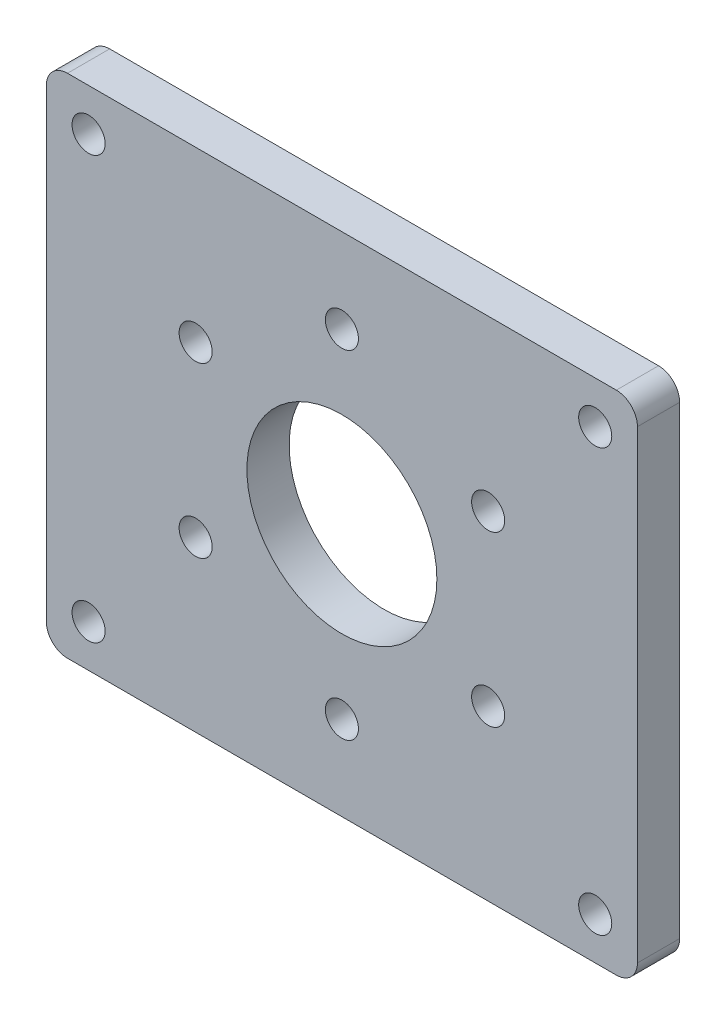
SolidWorks part; units mm, degrees
material "6061-T6 (SS)"
ref_plane "Front Plane" through (0, 0, 0) normal (0, 0, 1) x (1, 0, 0)
ref_plane "Top Plane" through (0, 0, 0) normal (0, 1, 0) x (1, 0, 0)
ref_plane "Right Plane" through (0, 0, 0) normal (1, 0, 0) x (0, 0, -1)
sketch "Sketch1" plane through (0, 0, 0) normal (0, 0, 1) x (1, 0, 0)
  line L0 (-38.1, -31.75) -> (-38.1, 31.75) construction
  line L1 (-44.45, -38.1) -> (44.45, -38.1)
  line L2 (-44.45, -38.1) -> (-44.45, 38.1)
  line L3 (-44.45, 38.1) -> (44.45, 38.1)
  line L4 (44.45, -38.1) -> (44.45, 38.1)
  line L5 (-44.45, -38.1) -> (44.45, 38.1) construction
  line L6 (-44.45, 38.1) -> (44.45, -38.1) construction
  line L7 (-38.1, 31.75) -> (38.1, 31.75) construction
  line L8 (38.1, -31.75) -> (38.1, 31.75) construction
  line L9 (-38.1, -31.75) -> (38.1, -31.75) construction
  circle A0 centre (0, 0) radius 30
  circle A1 centre (0, 25.4) radius 2.4892
  circle A2 centre (0, 0) radius 25.4 construction
  circle A3 centre (21.997, 12.7) radius 2.4892
  circle A4 centre (21.997, -12.7) radius 2.4892
  circle A5 centre (0, -25.4) radius 2.4892
  circle A6 centre (-21.997, -12.7) radius 2.4892
  circle A7 centre (-21.997, 12.7) radius 2.4892
  circle A8 centre (0, 0) radius 14.2875
  circle A9 centre (-38.1, 31.75) radius 2.4892
  circle A10 centre (-38.1, -31.75) radius 2.4892
  circle A11 centre (38.1, -31.75) radius 2.4892
  circle A12 centre (38.1, 31.75) radius 2.4892
  point P0 (0, 0)
  point P24 (0, 0)
  dimension "D1" = 60
  dimension "D2" = 4.9784
  dimension "D3" = 50.8
  dimension "D6" = 28.575
  dimension "D8" = 4.9784
  dimension "D5" = 88.9
  dimension "D9" = 76.2
  dimension "D7" = 6.35
  dimension "D4" = 6
extrude "Boss-Extrude1" add sketch "Sketch1" along normal blind 6.35 contours L1 L4 L3 L2 A12 A11 A10 A9 A0 | A0 A8 A7 A6 A5 A4 A3 A1 region at (-43.2791, 0, 0) region at (-29.1515, 0, 0)
fillet "Fillet1" radius 3.175 4 edges at (-44.45, -38.1, 3.175) (44.45, 38.1, 3.175) (44.45, -38.1, 3.175) (-44.45, 38.1, 3.175)
